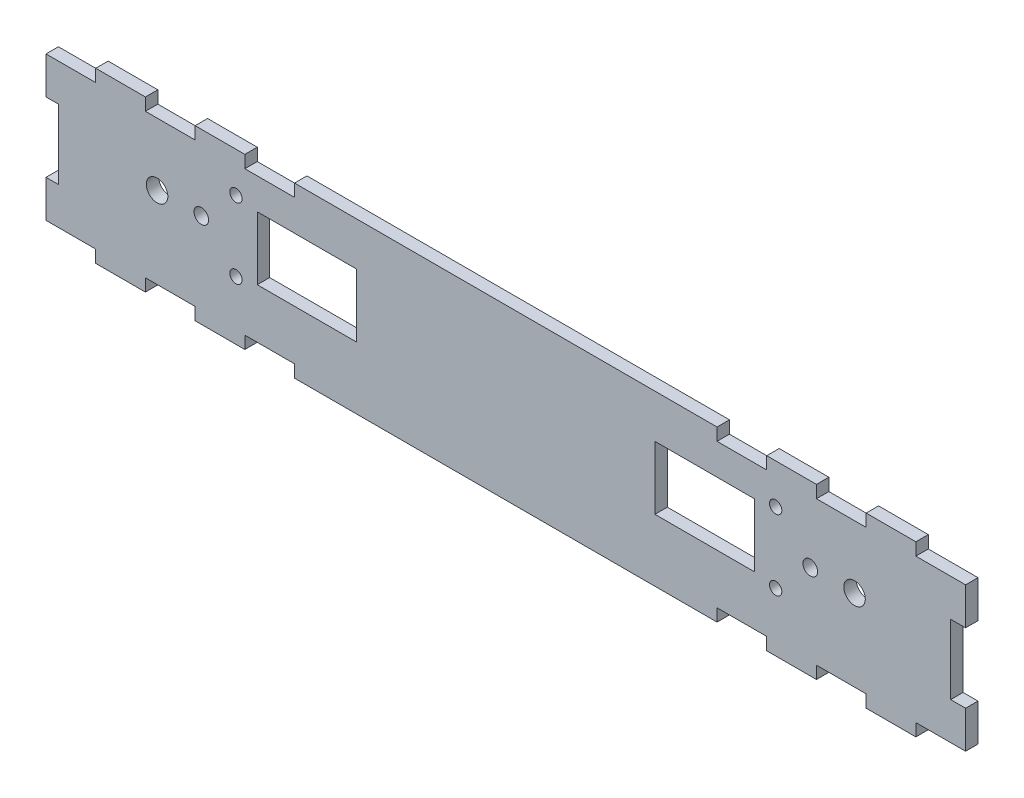
SolidWorks part; units mm, degrees
material "Acrylic (Medium-high impact)"
ref_plane "Front Plane" through (0, 0, 0) normal (0, 0, 1) x (1, 0, 0)
ref_plane "Top Plane" through (0, 0, 0) normal (0, 1, 0) x (1, 0, 0)
ref_plane "Right Plane" through (0, 0, 0) normal (1, 0, 0) x (0, 0, -1)
sketch "Sketch3" plane through (0, 0, 0) normal (0, 0, 1) x (1, 0, 0)
  line L0 (0, 22.5) -> (0, 0)
  line L1 (0, 0) -> (31.6, 0)
  line L2 (36.6, 5) -> (36.6, 17.5)
  line L3 (31.6, 22.5) -> (0, 22.5)
  line L4 (0, 0) -> (-63.5, 0) construction
  line L5 (-63.5, 0) -> (-63.5, 28.85) construction
  line L6 (-158.6, 22.5) -> (-127, 22.5)
  line L7 (0, 22.5) -> (-25.4, 22.5)
  line L8 (0, 22.5) -> (0, 0)
  line L9 (0, 0) -> (-25.4, 0)
  line L10 (-25.4, 22.5) -> (-25.4, 0)
  line L11 (-163.6, 5) -> (-163.6, 17.5)
  line L12 (-127, 0) -> (-158.6, 0)
  line L13 (-127, 22.5) -> (-127, 0)
  line L14 (-127, 0) -> (-101.6, 0)
  line L15 (-101.6, 22.5) -> (-101.6, 0)
  line L16 (-127, 22.5) -> (-101.6, 22.5)
  line L17 (-127, 22.5) -> (-127, 0)
  line L18 (-180.975, 28.85) -> (-180.975, -6.3925)
  line L21 (20.8125, -11.155) -> (58.7375, -11.155)
  line L22 (58.7375, 0) -> (58.7375, -11.155)
  line L25 (-179.3875, 28.85) -> (-185.7375, 28.85)
  line L26 (-185.7375, 22.5) -> (-185.7375, 28.85)
  line L27 (-185.7375, 28.85) -> (58.7375, 28.85)
  line L28 (-185.7375, 28.85) -> (-185.7375, -11.155)
  line L29 (-185.7375, -11.155) -> (58.7375, -11.155)
  line L30 (58.7375, 28.85) -> (58.7375, -11.155)
  line L31 (-180.975, -6.3925) -> (58.7375, -6.3925)
  line L32 (-185.7375, 24.0875) -> (53.975, 24.0875)
  line L33 (53.975, 24.0875) -> (53.975, -11.155)
  line L35 (-127, 22.5) -> (-101.6, 22.5)
  line L36 (-127, 22.5) -> (-127, 19.325)
  line L37 (-127, 19.325) -> (-101.6, 19.325)
  line L38 (-101.6, 22.5) -> (-101.6, 19.325)
  line L39 (-127, 0) -> (-101.6, 0)
  line L40 (-127, 0) -> (-127, 3.175)
  line L41 (-127, 3.175) -> (-101.6, 3.175)
  line L42 (-101.6, 0) -> (-101.6, 3.175)
  line L43 (0, 22.5) -> (-25.4, 22.5)
  line L44 (0, 22.5) -> (0, 19.325)
  line L45 (0, 19.325) -> (-25.4, 19.325)
  line L46 (-25.4, 22.5) -> (-25.4, 19.325)
  line L47 (0, 0) -> (-25.4, 0)
  line L48 (0, 0) -> (0, 3.175)
  line L49 (0, 3.175) -> (-25.4, 3.175)
  line L50 (-25.4, 0) -> (-25.4, 3.175)
  circle A2 centre (5.45, 2.25) radius 1.575
  circle A3 centre (5.45, 20.25) radius 1.575
  arc A6 (31.6, 0) -> (36.6, 5) centre (31.6, 5) ccw
  arc A7 (36.6, 17.5) -> (31.6, 22.5) centre (31.6, 17.5) ccw
  arc A8 (22.85, 11.25) -> (28.35, 11.25) centre (25.6, 11.25) ccw
  arc A9 (28.35, 11.25) -> (22.85, 11.25) centre (25.6, 11.25) ccw
  arc A10 (12.425, 11.25) -> (16.175, 11.25) centre (14.3, 11.25) ccw
  arc A11 (16.175, 11.25) -> (12.425, 11.25) centre (14.3, 11.25) ccw
  arc A12 (-143.175, 11.25) -> (-139.425, 11.25) centre (-141.3, 11.25) cw
  arc A13 (-139.425, 11.25) -> (-143.175, 11.25) centre (-141.3, 11.25) cw
  arc A14 (-155.35, 11.25) -> (-149.85, 11.25) centre (-152.6, 11.25) cw
  arc A15 (-149.85, 11.25) -> (-155.35, 11.25) centre (-152.6, 11.25) cw
  arc A16 (-163.6, 17.5) -> (-158.6, 22.5) centre (-158.6, 17.5) cw
  arc A17 (-158.6, 0) -> (-163.6, 5) centre (-158.6, 5) cw
  circle A18 centre (-132.45, 20.25) radius 1.575
  circle A19 centre (-132.45, 2.25) radius 1.575
  dimension "D3" = 5.45
  dimension "D4" = 3.15
  dimension "D8" = 3.15
  dimension "D6" = 2.25
  dimension "D9" = 1.875
  dimension "D10" = 4.7625
  dimension "D11" = 2.75
  dimension "D12" = 4.7625
  dimension "D17" = 5
  dimension "D18" = 5
  dimension "D1" = 31.6
  dimension "D2" = 36.6
  dimension "D5" = 2.25
  dimension "D7" = 5.45
  dimension "D13" = 11.25
  dimension "D14" = 14.3
  dimension "D15" = 11
  dimension "D16" = 11.25
  dimension "D19" = 22.5
  dimension "D20" = 244.475
  dimension "D21" = 30.48
  dimension "D22" = 25.4
  dimension "D23" = 3.175
  dimension "D24" = 25.4
  dimension "D25" = 3.175
  dimension "D26" = 25.4
extrude "Boss-Extrude1" add sketch "Sketch3" along normal blind 3.175 contours L33 L32 L18 L31 A7 L2 A6 L1 L9 L10 L7 L3 L12 A17 L11 A16 L6 L16 L15 L14 | A17 L12 L13 L6 A16 L11 A18 A12 A13 A14 A15 A19 | L2 A7 L3 L0 L1 A6 A11 A10 A9 A8 A2 A3 | L0 L49 L10 L9 | L45 L0 L7 L10 | L13 L37 L15 L16 | L40 L41 L42 L39 region at (18.1513, 11.25, 0) region at (-12.7, 20.9125, 0) region at (-12.7, 1.5875, 0) region at (-145.1513, 11.25, 0) region at (-114.3, 20.9125, 0) region at (-63.5, 7.3333, 0)
sketch "Sketch4" plane through (0, 0, 3.175) normal (0, 0, 1) x (1, 0, 0)
  line L0 (-155.575, 30.4375) -> (-155.575, 27.2625)
  line L1 (-180.975, 24.0875) -> (53.975, 24.0875)
  line L2 (-180.975, 24.0875) -> (-180.975, 30.4375)
  line L3 (-180.975, 30.4375) -> (53.975, 30.4375)
  line L4 (53.975, -6.3925) -> (53.975, 24.0875)
  line L5 (53.975, 24.0875) -> (-180.975, 24.0875)
  line L6 (-180.975, 24.0875) -> (-180.975, -6.3925)
  line L7 (-180.975, -6.3925) -> (53.975, -6.3925)
  line L8 (53.975, -6.3925) -> (53.975, 24.0875)
  line L9 (53.975, 24.0875) -> (-180.975, 24.0875)
  line L10 (-180.975, 24.0875) -> (-180.975, -6.3925)
  line L11 (-180.975, -6.3925) -> (53.975, -6.3925)
  line L12 (53.975, 24.0875) -> (53.975, 30.4375)
  line L13 (-180.975, 30.4375) -> (53.975, 30.4375)
  line L14 (-180.975, 30.4375) -> (-180.975, 27.2625)
  line L15 (-180.975, 27.2625) -> (53.975, 27.2625)
  line L16 (53.975, 30.4375) -> (53.975, 27.2625)
  line L17 (-180.975, 30.4375) -> (-168.275, 30.4375)
  line L18 (-180.975, 30.4375) -> (-180.975, 27.2625)
  line L19 (-180.975, 27.2625) -> (-168.275, 27.2625)
  line L20 (-168.275, 30.4375) -> (-168.275, 27.2625)
  line L21 (-155.575, 30.4375) -> (-142.875, 30.4375)
  line L22 (-142.875, 30.4375) -> (-142.875, 27.2625)
  line L23 (-155.575, 27.2625) -> (-142.875, 27.2625)
  line L24 (-130.175, 30.4375) -> (-130.175, 27.2625)
  line L25 (-130.175, 30.4375) -> (-117.475, 30.4375)
  line L26 (-117.475, 30.4375) -> (-117.475, 27.2625)
  line L27 (-130.175, 27.2625) -> (-117.475, 27.2625)
  line L28 (28.575, 27.2625) -> (28.575, 30.4375)
  line L29 (53.975, 27.2625) -> (41.275, 27.2625)
  line L30 (53.975, 27.2625) -> (53.975, 30.4375)
  line L31 (53.975, 30.4375) -> (41.275, 30.4375)
  line L32 (41.275, 27.2625) -> (41.275, 30.4375)
  line L33 (28.575, 27.2625) -> (15.875, 27.2625)
  line L34 (15.875, 27.2625) -> (15.875, 30.4375)
  line L35 (28.575, 30.4375) -> (15.875, 30.4375)
  line L36 (3.175, 27.2625) -> (3.175, 30.4375)
  line L37 (3.175, 27.2625) -> (-9.525, 27.2625)
  line L38 (-9.525, 27.2625) -> (-9.525, 30.4375)
  line L39 (3.175, 30.4375) -> (-9.525, 30.4375)
  line L40 (-180.975, 8.8475) -> (49.4654, 8.8475) construction
  line L41 (3.175, -12.7425) -> (-9.525, -12.7425)
  line L42 (-9.525, -9.5675) -> (-9.525, -12.7425)
  line L43 (3.175, -9.5675) -> (-9.525, -9.5675)
  line L44 (3.175, -9.5675) -> (3.175, -12.7425)
  line L45 (28.575, -12.7425) -> (15.875, -12.7425)
  line L46 (15.875, -9.5675) -> (15.875, -12.7425)
  line L47 (28.575, -9.5675) -> (15.875, -9.5675)
  line L48 (41.275, -9.5675) -> (41.275, -12.7425)
  line L49 (53.975, -12.7425) -> (41.275, -12.7425)
  line L50 (53.975, -9.5675) -> (53.975, -12.7425)
  line L51 (53.975, -9.5675) -> (41.275, -9.5675)
  line L52 (28.575, -9.5675) -> (28.575, -12.7425)
  line L53 (-130.175, -9.5675) -> (-117.475, -9.5675)
  line L54 (-117.475, -12.7425) -> (-117.475, -9.5675)
  line L55 (-130.175, -12.7425) -> (-117.475, -12.7425)
  line L56 (-130.175, -12.7425) -> (-130.175, -9.5675)
  line L57 (-155.575, -9.5675) -> (-142.875, -9.5675)
  line L58 (-142.875, -12.7425) -> (-142.875, -9.5675)
  line L59 (-155.575, -12.7425) -> (-142.875, -12.7425)
  line L60 (-168.275, -12.7425) -> (-168.275, -9.5675)
  line L61 (-180.975, -9.5675) -> (-168.275, -9.5675)
  line L62 (-180.975, -12.7425) -> (-180.975, -9.5675)
  line L63 (-180.975, -12.7425) -> (-168.275, -12.7425)
  line L64 (53.975, -12.7425) -> (53.975, -9.5675)
  line L65 (-180.975, -9.5675) -> (53.975, -9.5675)
  line L66 (-180.975, -12.7425) -> (-180.975, -9.5675)
  line L67 (-180.975, -12.7425) -> (53.975, -12.7425)
  line L68 (53.975, -6.3925) -> (53.975, -12.7425)
  line L69 (53.975, -6.3925) -> (-180.975, -6.3925)
  line L70 (-180.975, -12.7425) -> (53.975, -12.7425)
  line L71 (-180.975, -6.3925) -> (-180.975, -12.7425)
  line L72 (-180.975, -6.3925) -> (53.975, -6.3925)
  line L73 (-155.575, -12.7425) -> (-155.575, -9.5675)
  line M29 (53.975, 24.0875) -> (-180.975, 24.0875)
  line M31 (-180.975, -6.3925) -> (53.975, -6.3925)
  dimension "D2" = 6.35
  dimension "D3" = 3.175
  dimension "D4" = 12.7
  dimension "D5" = 3
  dimension "D6" = 12.7
  dimension "D7" = 3
  dimension "D1" = 0
extrude "Boss-Extrude2" add sketch "Sketch4" against normal blind 3.175 contours L15 L38 L13 L26 | L24 L13 L22 L15 | L13 L20 L15 L0 | L15 L2 L12 M29 | L36 L15 L34 L3 | L15 L32 L3 L28 | L71 L61 L65 L57 L53 L43 L47 L51 L68 M31 | L52 L67 L48 L65 | L44 L67 L46 L65 | L54 L67 L42 L65 | L58 L67 L56 L65 | L67 L73 L65 L60 region at (-161.925, 28.85, 3.175) region at (-63.5, 25.675, 3.175) region at (-136.525, 28.85, 3.175) region at (-63.5, 28.85, 3.175) region at (-63.5, -7.98, 3.175) region at (9.525, 28.85, 3.175) region at (34.925, 28.85, 3.175) region at (-161.925, -11.155, 3.175) region at (34.925, -11.155, 3.175) region at (-136.525, -11.155, 3.175) region at (9.525, -11.155, 3.175) region at (-63.5, -11.155, 3.175)
sketch "Sketch5" plane through (0, 0, 3.175) normal (0, 0, 1) x (1, 0, 0)
  line L0 (53.975, 27.2625) -> (53.975, -9.5675) construction
  line L1 (-168.275, -12.7425) -> (-180.975, -12.7425)
  line L2 (-168.275, -12.7425) -> (-168.275, -0.0425)
  line L3 (-168.275, -0.0425) -> (-180.975, -0.0425)
  line L4 (-180.975, -12.7425) -> (-180.975, -0.0425)
  line L5 (-180.975, 27.2625) -> (-180.975, -9.5675) construction
  line L6 (-168.275, 30.4375) -> (-180.975, 30.4375)
  line L7 (-168.275, 30.4375) -> (-168.275, 17.7375)
  line L8 (-168.275, 17.7375) -> (-180.975, 17.7375)
  line L9 (-180.975, 30.4375) -> (-180.975, 17.7375)
  line L10 (41.275, 30.4375) -> (53.975, 30.4375)
  line L11 (41.275, 30.4375) -> (41.275, 17.7375)
  line L12 (41.275, 17.7375) -> (53.975, 17.7375)
  line L13 (53.975, 30.4375) -> (53.975, 17.7375)
  line L15 (41.275, -12.7425) -> (53.975, -12.7425)
  line L16 (41.275, -12.7425) -> (41.275, -0.0425)
  line L17 (41.275, -0.0425) -> (53.975, -0.0425)
  line L18 (53.975, -12.7425) -> (53.975, -0.0425)
  line L19 (-180.975, 17.7375) -> (-177.8, 17.7375)
  line L20 (-180.975, 17.7375) -> (-180.975, -0.0425)
  line L21 (-180.975, -0.0425) -> (-177.8, -0.0425)
  line L22 (-177.8, 17.7375) -> (-177.8, -0.0425)
  line L23 (53.975, 17.7375) -> (50.165, 17.7375)
  line L24 (53.975, 17.7375) -> (53.975, -0.0425)
  line L25 (53.975, -0.0425) -> (50.165, -0.0425)
  line L26 (50.165, 17.7375) -> (50.165, -0.0425)
  dimension "D1" = 12.7
  dimension "D2" = 12.7
  dimension "D3" = 12.7
  dimension "D4" = 3.175
  dimension "D5" = 3.81
extrude "Cut-Extrude1" cut sketch "Sketch5" against normal blind 7.62 contours L22 L8 L20 L3 | L12 L26 L17 L24 region at (-179.3875, 8.8475, 3.175) region at (52.07, 8.8475, 3.175)
